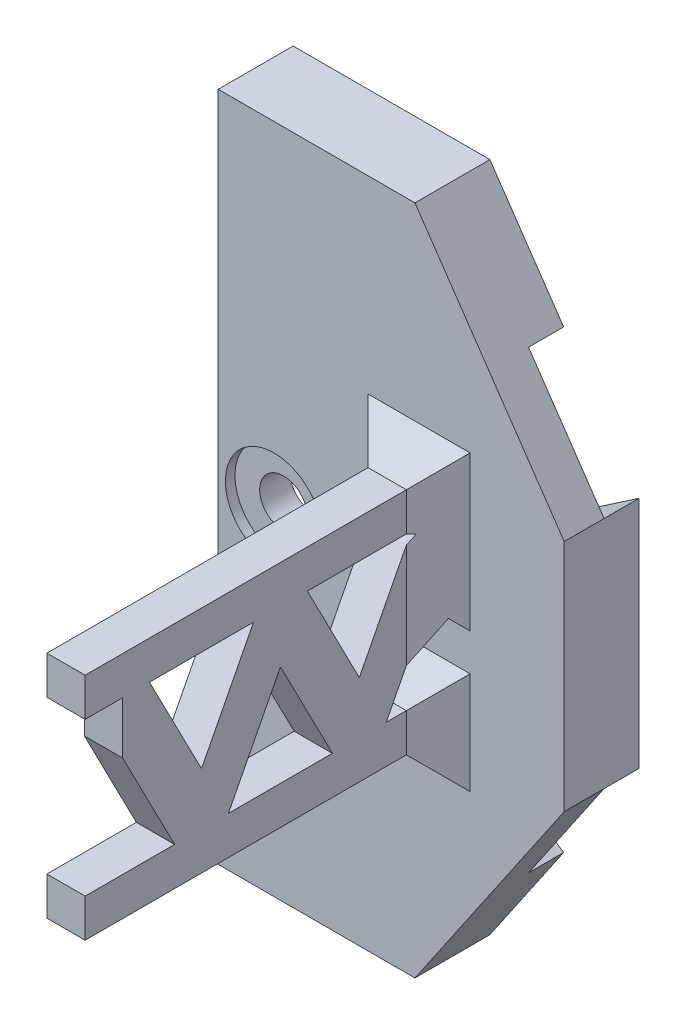
SolidWorks part; units mm, degrees
ref_plane "Front Plane" through (0, 0, 0) normal (0, 0, 1) x (1, 0, 0)
ref_plane "Top Plane" through (0, 0, 0) normal (0, 1, 0) x (1, 0, 0)
ref_plane "Right Plane" through (0, 0, 0) normal (1, 0, 0) x (0, 0, -1)
sketch "Sketch1" plane through (0, 0, 0) normal (0, 0, 1) x (1, 0, 0)
  line L0 (10.2887, 2.1795) -> (17.7557, 7.2761) construction
  line L1 (11.547, 0) -> (10.2887, 2.1795) construction
  line L2 (5.7735, 10) -> (-3.5, 10) construction
  line L3 (10.2887, -2.1795) -> (11.547, 0) construction
  line L4 (6.2773, 9.1274) -> (5.7735, 10) construction
  line L5 (-3.5, -10) -> (5.7735, -10) construction
  line L6 (5.7735, -10) -> (6.2773, -9.1274) construction
  line L7 (17.7557, 7.2761) -> (17.7557, -7.2761) construction
  line L8 (17.7557, -7.2761) -> (10.2887, -2.1795) construction
  line L9 (-3.5, 10) -> (-3.5, 21.2557) construction
  line L10 (-3.5, 21.2557) -> (8.9449, 21.2557) construction
  line L11 (8.9449, 21.2557) -> (13.7443, 14.2239) construction
  line L12 (13.7443, 14.2239) -> (6.2773, 9.1274) construction
  line L13 (-3.5, -10) -> (-3.5, -21.2557) construction
  line L14 (-3.5, -21.2557) -> (8.9449, -21.2557) construction
  line L15 (8.9449, -21.2557) -> (13.7443, -14.2239) construction
  line L16 (13.7443, -14.2239) -> (6.2773, -9.1274) construction
  line L17 (8.6283, 34.9446) -> (-3.1321, 14.575) [skipped]
  line L18 (8.6283, -34.9446) -> (20.3887, -55.3142) [skipped]
  line L19 (11.547, 0) -> (10.2887, 2.1795) construction
  line L20 (-3.5, 21.0557) -> (-3.5, 10.2)
  line L21 (-3.5, 21.0557) -> (8.8392, 21.0557)
  line L22 (6.2773, 9.1274) -> (21.2113, 19.3205) construction
  line L23 (-3.5, 10) -> (-3.5, -10) construction
  line L24 (21.2113, -19.3205) -> (6.2773, -9.1274) construction
  line L25 (6.2773, -9.1274) -> (5.7735, -10) construction
  line L26 (25.2227, -12.3726) -> (10.2887, -2.1795) construction
  line L27 (10.2887, 2.1795) -> (25.2227, 12.3726) construction
  line L28 (-3.5, 0) -> (17.7557, 0) construction
  line L29 (0, 0) -> (0, 21.2557) construction
  line L30 (8.8392, 21.0557) -> (13.4664, 14.2764)
  line L31 (13.4664, 14.2764) -> (6.3427, 9.4142)
  line L32 (6.3427, 9.4142) -> (5.889, 10.2)
  line L33 (5.889, 10.2) -> (-3.5, 10.2)
  line L34 (13.4664, 14.2764) -> (23.2106, 0) construction
  line L35 (18.2018, -7.3384) -> (10.5546, -2.1189)
  line L36 (10.5546, -2.1189) -> (11.7779, 0)
  line L37 (11.7779, 0) -> (10.5546, 2.1189)
  line L38 (10.5546, 2.1189) -> (18.2018, 7.3384)
  line L39 (8.8392, -21.0557) -> (13.4664, -14.2764)
  line L40 (13.4664, -14.2764) -> (6.3427, -9.4142)
  line L41 (5.889, -10.2) -> (6.3427, -9.4142)
  line L42 (-3.5, -10.2) -> (5.889, -10.2)
  line L43 (5.889, 10.2) -> (-3.3, 10.2) construction
  line L44 (-3.5, -21.0557) -> (8.8392, -21.0557)
  line L45 (-3.3, -10.2) -> (-3.3, -21.0557) construction
  line L46 (-3.3, 10.2) -> (-3.3, 21.0557) construction
  line L47 (-3.3, 21.0557) -> (8.8392, 21.0557) construction
  line L48 (-3.5, -10.2) -> (-3.5, -21.0557)
  line L49 (-3.3, -21.0557) -> (8.8392, -21.0557) construction
  line L50 (-3.3, -10.2) -> (5.889, -10.2) construction
  line L51 (17.5557, 6.8974) -> (17.5557, -6.8974) construction
  line L52 (23.2106, 0) -> (13.4664, -14.2764) construction
  line L53 (18.2018, -7.3384) -> (18.2018, 7.3384)
  line L54 (17.5557, -6.8974) -> (10.5546, -2.1189) construction
  line L55 (10.5546, 2.1189) -> (17.5557, 6.8974) construction
  circle A0 centre (0, 0) radius 1.5 construction
  circle A1 centre (0, 0) radius 10 construction
  circle A3 centre (0, 0) radius 1.5 construction
  dimension "D1" = 0.2
extrude "Boss-Extrude1" add sketch "Sketch1" along normal blind 2.2
sketch "Sketch3" plane through (0, 0, 2.2) normal (0, 0, 1) x (1, 0, 0)
  line L0 (-3.5, 21.0557) -> (-3.5, -21.0557)
  line L1 (-3.5, -21.0557) -> (8.8392, -21.0557) construction
  line L2 (-3.5, -21.0557) -> (8.8392, -21.0557)
  line L3 (8.8392, -21.0557) -> (18.2018, -7.3384)
  line L4 (18.2018, 7.3384) -> (18.2018, -7.3384)
  line L5 (0, 0) -> (18.2018, 0) construction
  line L7 (18.2018, 7.3384) -> (8.8392, 21.0557)
  line L8 (8.8392, 21.0557) -> (-3.5, 21.0557)
  line L9 (8.8392, -21.0557) -> (13.4664, -14.2764) construction
  circle A0 centre (0, 0) radius 1.5
  circle A2 centre (9.1009, 0) radius 1.5 construction
  circle A3 centre (0, 0) radius 1.5 construction
extrude "Boss-Extrude2" add sketch "Sketch3" along normal blind 2.5
sketch "Sketch4" plane through (0, 0, 4.7) normal (0, 0, 1) x (1, 0, 0)
  circle A0 centre (0, 0) radius 3.05
  dimension "D1" = 6.1
extrude "Cut-Extrude1" cut sketch "Sketch4" against normal blind 0.6
sketch "Sketch5" plane through (0, 0, 4.7) normal (0, 0, 1) x (1, 0, 0)
  line L0 (7.9009, 7.2) -> (10.3009, 7.2)
  line L1 (7.7009, 7.4) -> (10.5009, 7.4) construction
  line L2 (7.7009, 7.4) -> (7.7009, 4.6) construction
  line L3 (7.7009, 4.6) -> (10.5009, 4.6) construction
  line L4 (10.5009, 7.4) -> (10.5009, 4.6) construction
  line L5 (7.7009, -4.6) -> (10.5009, -4.6) construction
  line L6 (7.7009, -4.6) -> (7.7009, -7.4) construction
  line L7 (7.7009, -7.4) -> (10.5009, -7.4) construction
  line L8 (10.5009, -4.6) -> (10.5009, -7.4) construction
  line L9 (10.3009, 7.2) -> (10.3009, 4.8)
  line L10 (7.9009, 4.8) -> (10.3009, 4.8)
  line L11 (7.9009, 7.2) -> (7.9009, 4.8)
  line L12 (7.9009, -4.8) -> (10.3009, -4.8)
  line L13 (10.3009, -4.8) -> (10.3009, -7.2)
  line L14 (7.9009, -7.2) -> (10.3009, -7.2)
  line L15 (7.9009, -4.8) -> (7.9009, -7.2)
  dimension "D1" = 0.2
extrude "Boss-Extrude3" add sketch "Sketch5" along normal offset from surface (22.15 mm away) 0.1
sketch "Sketch6" plane through (10.3009, 0, 0) normal (1, 0, 0) x (0, 0, -1)
  line L0 (-4.7, 4.8) -> (-9.65, -4.8) construction
  line L2 (-26.85, -4.8) -> (-4.7, -4.8) construction
  line L4 (-9.65, -4.8) -> (-14.6, 4.8) construction
  line L5 (-26.85, 4.8) -> (-4.7, 4.8) construction
  line L6 (-14.6, 4.8) -> (-19.55, -4.8) construction
  line L7 (-19.55, -4.8) -> (-24.5, 4.8) construction
  line L8 (-6.3877, 4.8) -> (-9.65, -1.527)
  line L9 (-9.65, -1.527) -> (-12.9123, 4.8)
  line L10 (-16.2877, 4.8) -> (-19.55, -1.527)
  line L11 (-19.55, -1.527) -> (-22.8123, 4.8)
  line L12 (-4.7, 1.527) -> (-7.9623, -4.8)
  line L13 (-11.3377, -4.8) -> (-14.6, 1.527)
  line L14 (-14.6, 1.527) -> (-17.8623, -4.8)
  line L15 (-21.2377, -4.8) -> (-24.5, 1.527)
  line L16 (-4.7, 4.8) -> (-6.3877, 4.8)
  line L17 (-24.5, 4.8) -> (-24.5, 1.527)
  line L18 (-21.2377, -4.8) -> (-17.8623, -4.8)
  line L19 (-4.7, 1.527) -> (-4.7, 4.8)
  line L21 (-25, 12) -> (-25, -12) construction
  line L22 (-6.0332, 5.4874) -> (-9.65, -1.527) construction
  line L23 (-12.9123, 4.8) -> (-16.2877, 4.8)
  line L24 (-9.65, -1.527) -> (-14.6, 8.073) construction
  line L25 (-14.6, 8.073) -> (-19.55, -1.527) construction
  line L26 (-22.8123, 4.8) -> (-24.5, 4.8)
  line L27 (-19.55, -1.527) -> (-23.1668, 5.4874) construction
  line L28 (-19.55, -8.073) -> (-25.8332, 4.1126) construction
  line L29 (-14.6, 1.527) -> (-19.55, -8.073) construction
  line L30 (-11.3377, -4.8) -> (-7.9623, -4.8)
  line L31 (-9.65, -8.073) -> (-14.6, 1.527) construction
  line L32 (-3.3668, 4.1126) -> (-9.65, -8.073) construction
  dimension "D3" = 0.5
  dimension "D1" = 1.5
  dimension "D2" = 1.5
extrude "Boss-Extrude4" add sketch "Sketch6" against normal up to surface (2.4 mm away) up to face at (7.9009, 6, 15.775)
chamfer "Chamfer1" distance 2 angle 45 8 edges at (9.1009, -4.8, 4.7) (10.3009, -6, 4.7) (9.1009, -7.2, 4.7) (7.9009, -6, 4.7) (10.3009, 4.3635, 4.7) (9.1009, 7.2, 4.7) (7.9009, 4.3635, 4.7) (9.1009, 1.527, 4.7) first distance on face at (9.1009, 4.3635, 4.7)
